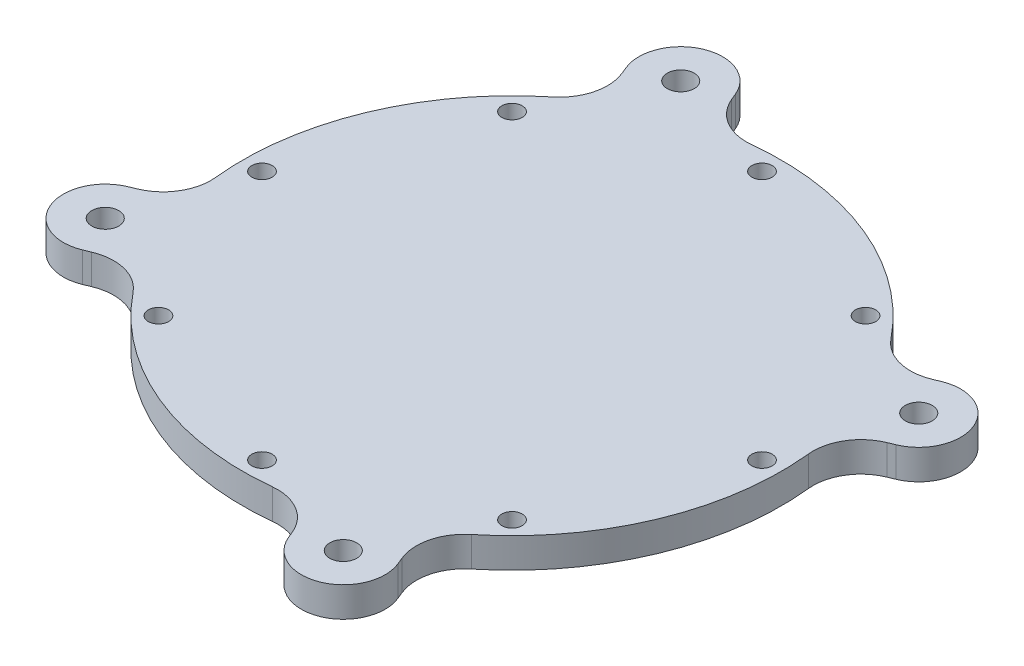
SolidWorks part; units mm, degrees
material "6061-T6 (SS)"
ref_plane "Front Plane" through (0, 0, 0) normal (0, 0, 1) x (1, 0, 0)
ref_plane "Top Plane" through (0, 0, 0) normal (0, 1, 0) x (1, 0, 0)
ref_plane "Right Plane" through (0, 0, 0) normal (1, 0, 0) x (0, 0, -1)
sketch "Sketch1" plane through (0, 0, 0) normal (0, 1, 0) x (1, 0, 0)
  circle A0 centre (0, 0) radius 45
  circle A1 centre (0, 41.75) radius 1.5
  circle A2 centre (29.5217, 29.5217) radius 1.5
  circle A3 centre (41.75, 0) radius 1.5
  circle A4 centre (29.5217, -29.5217) radius 1.5
  circle A5 centre (0, -41.75) radius 1.5
  circle A6 centre (-29.5217, -29.5217) radius 1.5
  circle A7 centre (-41.75, 0) radius 1.5
  circle A8 centre (-29.5217, 29.5217) radius 1.5
  point P22 (0, 0)
  dimension "D1" = 8
extrude "Boss-Extrude2" add sketch "Sketch1" along normal blind 5
sketch "Sketch9" plane through (0, 0, 0) normal (0, -1, 0) x (1, 0, 0)
  circle A2 centre (27, 0) radius 3.937
  circle A3 centre (0, -27) radius 3.937
  circle A4 centre (-27, 0) radius 3.937
  circle A5 centre (0, 27) radius 3.937
  point P15 (0, 0)
  dimension "D1" = 4
extrude "Boss-Extrude7" add sketch "Sketch9" along normal blind 4
sketch "Sketch10" plane through (0, 5, 0) normal (0, 1, 0) x (1, 0, 0)
  circle A0 centre (0, 41.75) radius 1.7
  circle A1 centre (29.5217, 29.5217) radius 1.7
  circle A2 centre (41.75, 0) radius 1.7
  circle A3 centre (29.5217, -29.5217) radius 1.7
  circle A4 centre (0, -41.75) radius 1.7
  circle A5 centre (-29.5217, -29.5217) radius 1.7
  circle A6 centre (-41.75, 0) radius 1.7
  circle A7 centre (-29.5217, 29.5217) radius 1.7
  point P19 (0, 0)
  dimension "D1" = 8
extrude "Cut-Extrude9" cut sketch "Sketch10" against normal blind 14
sketch "Sketch16" plane through (0, 0, 0) normal (0, -1, 0) x (1, 0, 0)
  line L0 (0, 0) -> (45, 0)
  line L1 (0, 0) -> (41.5746, 17.2208)
  line L2 (-58.808, 24.3233) -> (24.3233, 58.808)
  line L3 (-58.808, 24.3233) -> (-24.3233, -58.808)
  line L4 (24.3233, 58.808) -> (58.808, -24.3233)
  line L5 (-24.3233, -58.808) -> (58.808, -24.3233)
  line L6 (-58.808, 24.3233) -> (58.808, -24.3233) construction
  line L7 (24.3233, 58.808) -> (-24.3233, -58.808) construction
  line L8 (0, 0) -> (48.0521, -19.8746)
  line L9 (48.0521, -19.8746) -> (50.7275, -13.406)
  line L10 (50.7275, -13.406) -> (45.3766, -26.3431)
  line L11 (54.6528, -30.1798) -> (60.0037, -17.2427)
  line L12 (54.6528, -30.1798) -> (36.1004, -22.5065)
  line L13 (60.0037, -17.2427) -> (41.4513, -9.5694)
  line L14 (36.1004, -22.5065) -> (41.4513, -9.5694)
  line L15 (54.6528, -30.1798) -> (41.4513, -9.5694) construction
  line L16 (60.0037, -17.2427) -> (36.1004, -22.5065) construction
  circle A0 centre (0, 0) radius 45 construction
  circle A1 centre (48.0521, -19.8746) radius 7
  circle A2 centre (48.0521, -19.8746) radius 2.25
  dimension "D1" = 22.5
  dimension "D2" = 90
  dimension "D3" = 90
  dimension "D4" = 52
extrude "Boss-Extrude8" add sketch "Sketch16" against normal up to surface (5 mm away) contours A1 L12 | A1 L13 | A2 L8 A1 L10 | A2 L10 A1 L8 | A2 L10 A1 region at (42.7047, 0, -13.1821) region at (39.5396, 0, -20.8346) region at (46.3163, 0, -15.6903) region at (43.8678, 0, -21.6103) region at (51.012, 0, -21.0989) up to face at (0, 5, -40.05)
fillet "Fillet1" radius 8 2 edges at (43.7528, 2.5, -10.5213) (38.4019, 2.5, -23.4584)
sketch "Sketch17" plane through (0, 5, 0) normal (0, 1, 0) x (1, 0, 0)
  circle A0 centre (0, 0) radius 8.3177
extrude "Boss-Extrude9" add sketch "Sketch17" along normal blind 10
pattern_circular "CirPattern1" count 4 over 360 about axis through (0, 15, 0) along (0, 1, 0) of "Boss-Extrude8", "Fillet1"
sketch "Sketch18" plane through (0, 0, 0) normal (0, 0, 1) x (1, 0, 0)
  line L1 (8.3177, 15) -> (-8.3177, 15)
  line L2 (8.3177, 15) -> (8.3177, 5)
  line L3 (8.3177, 5) -> (-8.3177, 5)
  line L4 (-8.3177, 15) -> (-8.3177, 5)
  line L5 (-30.937, 0) -> (30.937, 0)
  line L6 (-30.937, 0) -> (-30.937, -4)
  line L7 (-30.937, -4) -> (30.937, -4)
  line L8 (30.937, 0) -> (30.937, -4)
extrude "Cut-Extrude10" cut sketch "Sketch18" against normal through all both and the other way through all
sketch "Sketch19" plane through (0, 0, 0) normal (0, -1, 0) x (1, 0, 0)
  circle A1 centre (-18.4816, 7.6441) radius 1.5
  circle A2 centre (7.6441, 18.4816) radius 1.5
  circle A3 centre (18.4816, -7.6441) radius 1.5
  circle A4 centre (-7.6441, -18.4816) radius 1.5
  point P0 (0, 0)
  dimension "D2" = 4
hole_wizard "M3 Tapped Hole1" positions "Sketch23" profile "Sketch24" tap size "M3" standard "DIN"
sketch "Sketch23" plane through (0, 0, 0) normal (0, -1, 0) x (-1, 0, 0)
  point P0 (7.6441, 18.4816)
  point P3 (18.4816, -7.6441)
  point P6 (-7.6441, -18.4816)
  point P9 (-18.4816, 7.6441)
sketch "Sketch24" plane through (-7.6441, 0, -18.4816) normal (1, 0, 0) x (0, 0, -1)
  line L0 (0, 0) -> (0, 4)
  line L1 (0, 4) -> (1.25, 3.2489)
  line L2 (1.25, 3.2489) -> (1.25, 0)
  line L5 (1.25, 0) -> (0, 0)
  line L10 (0, 4) -> (-1.25, 3.2489) construction
  line L11 (0, -6.35) -> (0, 107.95) construction
  dimension "Tap Drill Dia." = 2.5
  dimension "Tap Drill Depth" = 4
  dimension "Drill Angle" = 118
